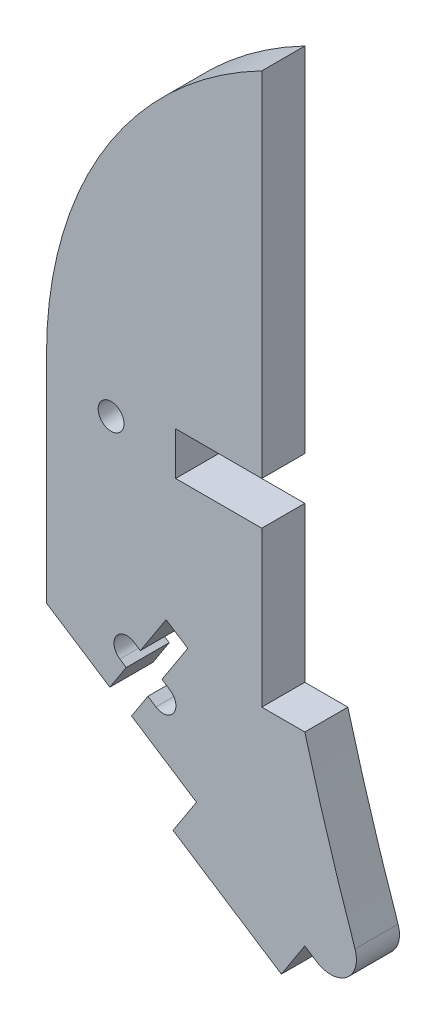
SolidWorks part; units mm, degrees
ref_plane "Front Plane" through (0, 0, 0) normal (0, 0, 1) x (1, 0, 0)
ref_plane "Top Plane" through (0, 0, 0) normal (0, 1, 0) x (1, 0, 0)
ref_plane "Right Plane" through (0, 0, 0) normal (1, 0, 0) x (0, 0, -1)
sketch "Sketch1" plane through (0, 0, 0) normal (0, 0, 1) x (1, 0, 0)
  line L0 (20.7522, -13.4767) -> (-12.5801, 8.1696)
  line L1 (20.7522, -13.4767) -> (-30, -13.4767)
  line L2 (-12.5801, 8.1696) -> (0, 0)
  line L3 (-5, 21.5233) -> (-5, 85.5233)
  line L4 (-30, -13.4767) -> (-30, 44.5233)
  line L5 (-5, 44.5233) -> (-15, 44.5233)
  line L6 (20.7522, -13.4767) -> (0, -13.4767)
  line L7 (-5, 44.5233) -> (-5, 39.5233)
  line L8 (-5, 21.5233) -> (0, 21.5233)
  line L9 (0, -13.4767) -> (0, 21.5233)
  line L10 (-5, 39.5233) -> (-15, 39.5233)
  line L11 (-15, 44.5233) -> (-15, 39.5233)
  line L12 (-12.5801, 8.1696) -> (-15.3033, 3.9762)
  line L13 (0, 0) -> (-2.7232, -4.1934)
  line L14 (-15.3033, 3.9762) -> (-2.7232, -4.1934)
  line L15 (-12.5801, 8.1696) -> (-30, 19.4822)
  line L16 (-20.1281, 13.0713) -> (-22.6441, 14.7053)
  line L17 (-20.1281, 13.0713) -> (-13.5924, 23.1354)
  line L18 (-22.6441, 14.7053) -> (-16.1084, 24.7693)
  line L19 (-13.5924, 23.1354) -> (-16.1084, 24.7693)
  line L23 (-16.4702, 16.6577) -> (-20.6635, 19.3809) construction
  line L24 (-17.2871, 15.3997) -> (-21.4805, 18.1229)
  line L25 (-15.6532, 17.9157) -> (-19.8466, 20.6389)
  line L26 (-18.5668, 18.0193) -> (-21.29, 13.8259) construction
  line L27 (-15, 42.0233) -> (-30, 42.0233) construction
  arc A0 (-5, 85.5233) -> (-30, 44.5233) centre (16.12, 44.5233) ccw
  arc A1 (-17.2871, 15.3997) -> (-15.6532, 17.9157) centre (-16.4702, 16.6577) ccw
  arc A2 (-19.8466, 20.6389) -> (-21.4805, 18.1229) centre (-20.6635, 19.3809) ccw
  circle A3 centre (-22.5, 42.0233) radius 1.5
  point P24 (-18.5668, 18.0193)
  dimension "D14" = 3
  dimension "D1" = 25
  dimension "D2" = 58
  dimension "D3" = 33
  dimension "D4" = 5
  dimension "D5" = 64
  dimension "D6" = 35
  dimension "D7" = 5
  dimension "D8" = 15
  dimension "D9" = 3
  dimension "D10" = 12
  dimension "D11" = 9
  dimension "D12" = 3
  dimension "D13" = 8
  dimension "D15" = 5
extrude "Boss-Extrude1" add sketch "Sketch1" along normal blind 5 contours L4 L0 | L12 L14 L13 L2 region at (-15.1399, 41.8984, 0)
sketch "Sketch2" plane through (0, 0, 5) normal (0, 0, 1) x (1, 0, 0)
  line L0 (0, 0) -> (1.3661, -0.8871)
  line L1 (-12.5801, 8.1696) -> (-20.1281, 13.0713) construction
  line L2 (0, 0) -> (0, 21.5233) construction
  circle A0 centre (3, 1.6289) radius 3
  arc A1 (0, 21.5233) -> (6.1773, 1.6289) centre (276.4025, 96.4406) ccw
  line M15 (0, 0) -> (0, 21.5233)
  dimension "D1" = 6
extrude "Boss-Extrude2" add sketch "Sketch2" against normal blind 5 contours A1 A0 M15 | A0 | A0 L0 M15 region at (0.2853, 0.1549, 5) region at (3, 1.6289, 5) region at (1.6993, 9.7723, 5)
